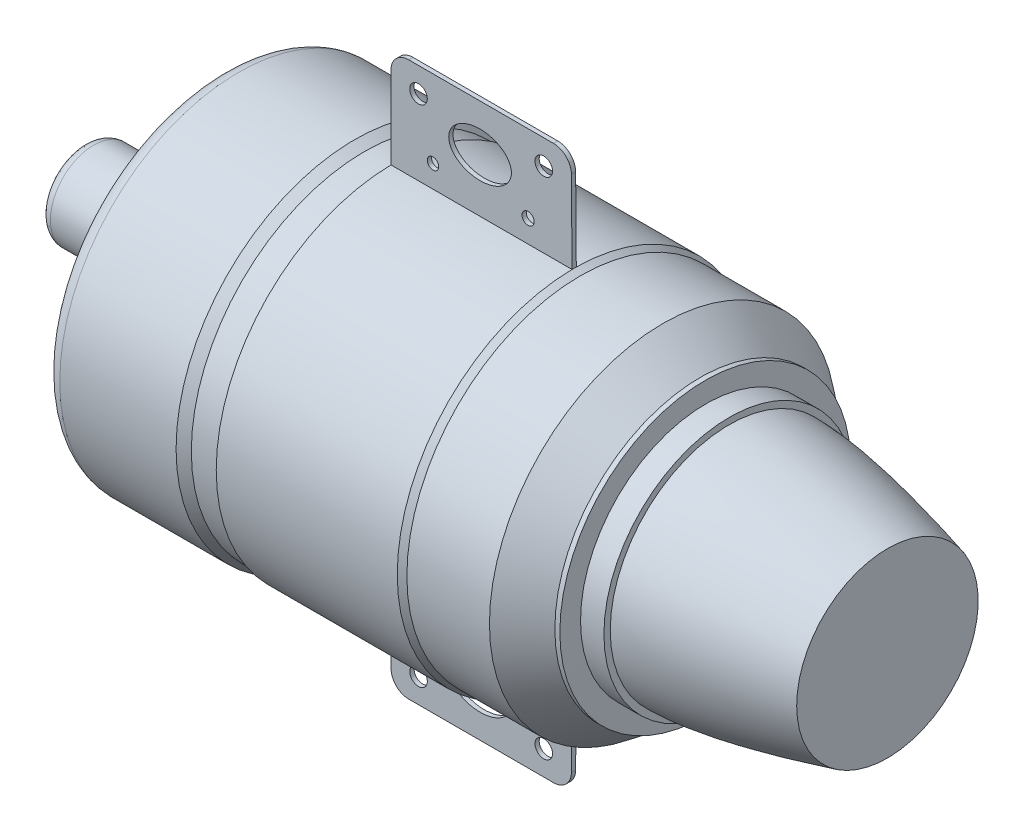
SolidWorks part; units mm, degrees
ref_plane "Front Plane" through (0, 0, 0) normal (0, 0, 1) x (1, 0, 0)
ref_plane "Top Plane" through (0, 0, 0) normal (0, 1, 0) x (1, 0, 0)
ref_plane "Right Plane" through (0, 0, 0) normal (1, 0, 0) x (0, 0, -1)
sketch "Sketch1" plane through (0, 0, 0) normal (0, 0, 1) x (1, 0, 0)
  line L0 (-26.7963, 0) -> (12.4273, 0) construction
  line L1 (1.0905, 5.1722) -> (9.4504, 5.1722)
  line L2 (9.4504, 5.1722) -> (9.4504, 0)
  line L3 (17.0937, 0) -> (17.0937, 18.9133)
  line L4 (19.2083, 21.3115) -> (33.0854, 21.3115)
  line L5 (33.0854, 21.3115) -> (34.2496, 20.6596)
  line L6 (34.2496, 20.6596) -> (37.6708, 20.6596)
  line L7 (59.2694, 21.1075) -> (60.0052, 20.6955)
  line L8 (60.0052, 20.6955) -> (69.8575, 20.6955)
  line L9 (69.8575, 20.6955) -> (74.3124, 17.3492)
  line L10 (74.3124, 17.3492) -> (74.9094, 17.3492)
  line L11 (74.9094, 17.3492) -> (74.9817, 14.9528)
  line L12 (74.9817, 14.9528) -> (77.7707, 14.9528)
  line L13 (77.7707, 14.9528) -> (77.7707, 14.1977)
  line L14 (96.6452, 0) -> (96.6452, 10.8275)
  line L15 (85.173, 14.1977) -> (70.5882, 14.1977) construction
  line L16 (0, 0) -> (0, -2.4925) construction
  line L17 (37.6708, 20.6596) -> (37.6708, 21.1075)
  line L18 (37.6708, 21.1075) -> (59.2694, 21.1075)
  line L19 (17.0937, 17.7576) -> (11.0147, 6.1199)
  line L20 (17.0937, 14.4568) -> (12.1234, 4.9415)
  line L21 (12.1234, 4.9415) -> (12.1234, 0)
  line L22 (37.6708, 21.1075) -> (37.6708, 30.916)
  line L23 (17.0937, 0) -> (96.6452, 0)
  line L24 (39.7842, 33.0294) -> (57.0627, 33.0294)
  line L25 (9.4504, 0) -> (0, 0)
  line L26 (59.1927, 30.916) -> (59.2694, 21.1075)
  line L27 (12.1234, 0) -> (9.4504, 0)
  line L28 (9.4504, 5.1722) -> (9.4504, 7.9511)
  line L29 (9.4504, 7.9511) -> (11.9713, 7.9511)
  line L30 (59.2694, 21.1075) -> (59.2694, 18.6791)
  line L31 (59.2694, 18.6791) -> (37.6708, 18.6791)
  line L32 (37.6708, 18.6791) -> (37.6708, 20.6596)
  arc A0 (17.0937, 18.9133) -> (19.2083, 21.3115) centre (19.511, 18.9133) cw
  arc A1 (0, 0) -> (1.0905, 5.1722) centre (12.8113, 0) cw
  arc A2 (9.4504, 5.1722) -> (11.0147, 6.1199) centre (9.4504, 6.9371) ccw
  arc A3 (37.6708, 30.916) -> (39.7842, 33.0294) centre (39.7842, 30.916) cw
  arc A4 (57.0627, 33.0294) -> (59.1927, 30.916) centre (57.0627, 30.8993) cw
  circle A5 centre (55.9165, 30.1262) radius 0.9796
  circle A6 centre (40.8958, 30.1262) radius 0.98
  circle A7 centre (42.6827, 23.7624) radius 0.6813
  circle A8 centre (54.0254, 23.7624) radius 0.7233
  ellipse E0 centre (48.297, 27.463) end of major axis (52.0357, 27.463) minor radius 2.6632
  spline S0 degree 2 poles (77.7707, 14.1977) (83.9678, 14.1977) (96.6452, 10.8275) knots 0 0 0 1 1 1
  point P60 (1.0905, 5.1722)
revolve "Revolve1" add sketch "Sketch1" angle 360 about L0 region at (4.898, 2.5349, 0) region at (53.424, 9.3335, 0) region at (48.4701, 19.8933, 0)
extrude "Boss-Extrude1" add sketch "Sketch1<4>" along normal mid plane 0.508 contours A4 L24 A3 L22 L18 L26 E0 A8 A7 A6 A5 | L32 L31 L30 L18 L17 | A6 | A5 region at (48.4701, 19.8933, 0) region at (37.9175, 26.0118, 0)
sketch "Sketch1<4>" plane through (0, 0, 0) normal (0, 0, 1) x (1, 0, 0) same geometry as "Sketch1"
extrude "Boss-Extrude2" add sketch "Sketch1<5>" along normal mid plane 2.54 contours A2 L2 L27 L21 L20 L3 L19 region at (12.7514, 7.2447, 0)
sketch "Sketch1<5>" plane through (0, 0, 0) normal (0, 0, 1) x (1, 0, 0) same geometry as "Sketch1"
revolve "Cut-Revolve1" cut sketch "Sketch1<6>" angle 360 about L0 region at (10.3968, 6.8036, 0)
sketch "Sketch1<6>" plane through (0, 0, 0) normal (0, 0, 1) x (1, 0, 0) same geometry as "Sketch1"
pattern_circular "CirPattern1" count 4 over 360 about axis through (-26.7963, 0, 0) along (1, 0, 0) of "Boss-Extrude2", "Cut-Revolve1"
mirror "Mirror1" about plane through (0, 0, 0) normal (0, 1, 0) of "Boss-Extrude1"
fillet "Fillet1" radius 1.27 1 edges at (1.0905, 0, 5.1722)
scale "Scale1" scale about centroid uniform scaling yes scale factor 2.276
sketch "Sketch2" plane through (0, 0, 0.5781) normal (0, 0, 1) x (1, 0, 0)
  line L0 (46.4059, 75.1749) -> (46.4059, 62.3363) construction
  line L1 (0, 0) -> (39.7086, 0)
  line L5 (21.9329, 70.3648) -> (21.9329, 48.0373)
  line L6 (21.9329, 48.0373) -> (71.0914, 48.0373)
  line L7 (71.0914, 48.0373) -> (71.0914, 48.0407)
  line L8 (71.0914, 48.0407) -> (70.9167, 70.3648)
  line L9 (66.0688, 75.1749) -> (26.743, 75.1749)
  line L14 (66.0688, 75.1749) -> (26.743, 75.1749)
  circle A0 centre (29.4059, 68.5) radius 2.3812
  circle A1 centre (63.4059, 68.5) radius 2.3813
  arc A2 (70.9167, 70.3648) -> (66.0688, 75.1749) centre (66.0688, 70.3269) ccw
  arc A3 (26.743, 75.1749) -> (21.9329, 70.3648) centre (26.743, 70.3648) ccw
  arc A4 (70.9167, 70.3648) -> (66.0688, 75.1749) centre (66.0688, 70.3269) ccw
  arc A5 (26.743, 75.1749) -> (21.9329, 70.3648) centre (26.743, 70.3648) ccw
  circle A6 centre (29.4059, -68.5) radius 2.3812
  circle A7 centre (63.4059, -68.5) radius 2.3813
  point P21 (0, 0)
  point P22 (0, 0)
  point P23 (0, 0)
  point P24 (0, 0)
  point P25 (0, 0)
  dimension "D2" = 4.7625
  dimension "D3" = 34
  dimension "D4" = 17
  dimension "D5" = 137
  dimension "D6" = 68.5
  dimension "D1" = 0
extrude "Cut-Extrude1" cut sketch "Sketch2" against normal through all contours A0 | A1 | A6 | A7 region at (29.4059, 68.5, 0.5781) region at (63.4059, 68.5, 0.5781) region at (29.4059, -68.5, 0.5781) region at (63.4059, -68.5, 0.5781)
equation "\"D4@Sketch2\"=\"D3@Sketch2\"/2"
equation "\"D6@Sketch2\"=\"D5@Sketch2\"/2"
equation "\"D2@Sketch2\"=6/32"
